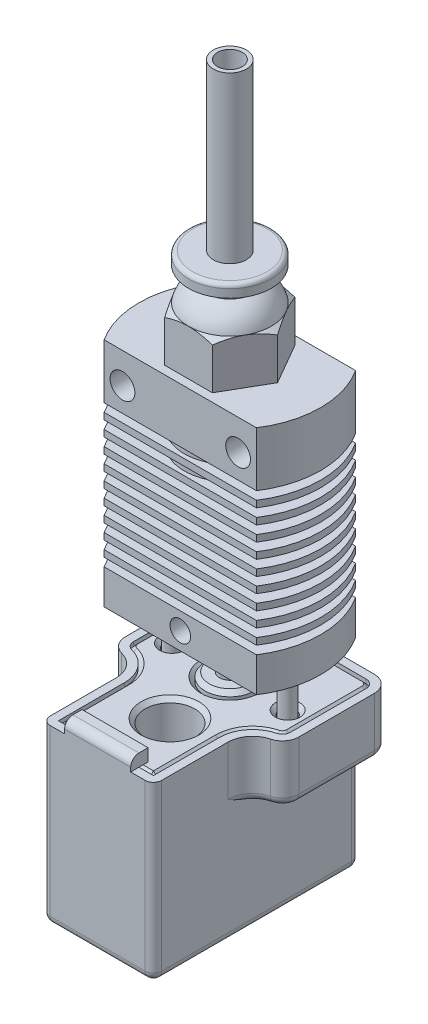
SolidWorks part; units mm, degrees
ref_plane "Front Plane" through (0, 0, 0) normal (0, 0, 1) x (1, 0, 0)
ref_plane "Top Plane" through (0, 0, 0) normal (0, 1, 0) x (1, 0, 0)
ref_plane "Right Plane" through (0, 0, 0) normal (1, 0, 0) x (0, 0, -1)
sketch "Sketch3" plane through (0, 0, 0) normal (0, 1, 0) x (1, 0, 0)
  line L1 (-9.2195, 6) -> (9.2195, 6)
  line L3 (-9.2195, -6) -> (9.2195, -6)
  arc A0 (-9.2195, 6) -> (-9.2195, -6) centre (0, 0) ccw
  arc A1 (9.2195, -6) -> (9.2195, 6) centre (0, 0) ccw
extrude "Boss-Extrude1" add sketch "Sketch3" along normal blind 28
sketch "Sketch5" plane through (0, 0, 0) normal (0, 0, 1) x (1, 0, 0)
  line L0 (0, 28) -> (0, 25.8) construction
  line L1 (-9.2195, 28) -> (9.2195, 28) construction
  line L2 (0, 25.8) -> (0, 22.8) construction
  line L3 (-7, 24.3) -> (7, 24.3) construction
  circle A0 centre (7, 24.3) radius 1.5
  circle A1 centre (-7, 24.3) radius 1.5
  point P9 (0, 24.3)
extrude "Cut-Extrude1" cut sketch "Sketch5" against normal through all and the other way through all
sketch "Sketch6" plane through (0, 0, 0) normal (0, 0, 1) x (1, 0, 0)
  line L0 (0, 28) -> (4.5, 28)
  line L1 (-9.2195, 28) -> (9.2195, 28) construction
  line L2 (0, 28) -> (0, 19.5) construction
  line L3 (4.5, 28) -> (4.5, 19.5)
  line L4 (0, 19.5) -> (3.5, 19.5) construction
  line L5 (4.5, 19.5) -> (3.5, 18.5)
  line L6 (3.5, 18.5) -> (3.5, 0)
  line L7 (3.5, 0) -> (0, 0)
  line L8 (0, 0) -> (0, 28)
  line L9 (11.9658, 28) -> (11.9658, 21.4) construction
  line L10 (0, 21.4) -> (5.5, 21.4) construction
  line L11 (5.5, 19.6) -> (5.5, 18.6)
  line L12 (5.5, 21.4) -> (11.97, 21.4)
  line L13 (5.5, 21.4) -> (5.5, 20.4)
  line L14 (5.5, 20.4) -> (11.97, 20.4)
  line L15 (11.97, 21.4) -> (11.97, 20.4)
  line L16 (5.5, 19.6) -> (11.97, 19.6)
  line L17 (11.97, 19.6) -> (11.97, 18.6)
  line L18 (5.5, 18.6) -> (11.97, 18.6)
  line L19 (0, 16.0604) -> (4, 16.0604) construction
  line L20 (11.97, 18.6) -> (11.97, 17.8) construction
  line L21 (11.97, 15) -> (4, 15)
  line L22 (11.97, 17.8) -> (4, 17.8)
  line L23 (11.97, 17.8) -> (11.97, 16.8)
  line L24 (11.97, 16.8) -> (4, 16.8)
  line L25 (4, 17.8) -> (4, 16.8)
  line L26 (4, 16) -> (4, 15)
  line L27 (11.97, 16) -> (4, 16)
  line L28 (11.97, 16) -> (11.97, 15)
  line L29 (11.97, 13.2) -> (4, 13.2)
  line L30 (4, 14.2) -> (4, 13.2)
  line L31 (11.97, 14.2) -> (4, 14.2)
  line L32 (11.97, 14.2) -> (11.97, 13.2)
  line L33 (11.97, 11.4) -> (4, 11.4)
  line L34 (4, 12.4) -> (4, 11.4)
  line L35 (11.97, 12.4) -> (4, 12.4)
  line L36 (11.97, 12.4) -> (11.97, 11.4)
  line L37 (11.97, 9.6) -> (4, 9.6)
  line L38 (4, 10.6) -> (4, 9.6)
  line L39 (11.97, 10.6) -> (4, 10.6)
  line L40 (11.97, 10.6) -> (11.97, 9.6)
  line L41 (11.97, 7.8) -> (4, 7.8)
  line L42 (4, 8.8) -> (4, 7.8)
  line L43 (11.97, 8.8) -> (4, 8.8)
  line L44 (11.97, 8.8) -> (11.97, 7.8)
  line L45 (11.97, 6) -> (4, 6)
  line L46 (4, 7) -> (4, 6)
  line L47 (11.97, 7) -> (4, 7)
  line L48 (11.97, 7) -> (11.97, 6)
  line L49 (11.97, 4.2) -> (4, 4.2)
  line L50 (4, 5.2) -> (4, 4.2)
  line L51 (11.97, 5.2) -> (4, 5.2)
  line L52 (11.97, 5.2) -> (11.97, 4.2)
  dimension "D1" = 2
  dimension "D2" = 8
revolve "Cut-Revolve1" cut sketch "Sketch6" angle 360 about L8
sketch "Sketch7" plane through (0, 0, 6) normal (0, 0, 1) x (1, 0, 0)
  line L0 (0, 0) -> (0, 4.2) construction
  line L1 (9.2195, 4.2) -> (-9.2195, 4.2) construction
  circle A0 centre (0, 2.1) radius 1.25
extrude "Cut-Extrude2" cut sketch "Sketch7" against normal blind 5
ref_plane "Plane1" through (0, -5.7, 0) normal (0, 1, 0) x (1, 0, 0)
sketch "Sketch9" plane through (0, -5.7, 0) normal (0, 1, 0) x (1, 0, 0)
  line L0 (0, 0) -> (0, -15) construction
  line L1 (0, 0) -> (0, 8) construction
  line L2 (-5.75, 0) -> (5.75, 0) construction
  line L3 (8.1234, 0) -> (8.1234, -8) construction
  line L4 (-5.75, 8) -> (5.75, 8)
  line L5 (-5.75, 8) -> (-5.75, -15)
  line L6 (-5.75, -15) -> (5.75, -15)
  line L7 (5.75, 8) -> (5.75, -15)
  line L8 (5.75, -8) -> (0.75, -8) construction
  circle A0 centre (0, 0) radius 3
  circle A1 centre (0.75, -8) radius 3
  point P6 (0, 0)
extrude "Boss-Extrude2" add sketch "Sketch9" against normal blind 20 separate body
sketch "Sketch10" plane through (0, -5.7, 0) normal (0, 1, 0) x (1, 0, 0)
  line L0 (0, 8) -> (0, -3) construction
  line L1 (5.75, 8) -> (-5.75, 8) construction
  line L2 (5.75, -15) -> (5.75, 8) construction
  line L3 (-9.5, 8) -> (-5.75, 8)
  line L4 (-9.5, 8) -> (-9.5, -3)
  line L5 (-9.5, -3) -> (-5.75, -3)
  line L6 (9.5, 8) -> (9.5, -3)
  line L7 (-9.5, 8) -> (9.5, -3) construction
  line L8 (-9.5, -3) -> (9.5, 8) construction
  line L9 (-5.75, 8) -> (-5.75, -15) construction
  line L10 (5.75, -3) -> (5.75, 8)
  line L11 (-5.75, 8) -> (-5.75, -3)
  line L12 (5.75, -3) -> (9.5, -3)
  line L13 (5.75, 8) -> (9.5, 8)
  point P5 (0, 2.5)
  line M4 (-5.75, 8) -> (-5.75, -15)
  line M6 (5.75, -15) -> (5.75, 8)
extrude "Boss-Extrude3" add sketch "Sketch10" against normal blind 6 contours L4 L5 L3 M4 | L13 L12 L6 M6 region at (-7.625, -5.7, -2.5) region at (7.625, -5.7, -2.5)
sketch "Sketch8" plane through (0, -5.7, 0) normal (0, 1, 0) x (1, 0, 0)
  line L0 (-7, 0) -> (7, 0) construction
  circle A0 centre (7, 0) radius 1
  circle A1 centre (-7, 0) radius 1
  point P5 (0, 0)
extrude "Cut-Extrude3" cut sketch "Sketch8" along normal up to vertex (9.9 mm away) and the other way through all up to point (-9.2195, 4.2, 6)
sketch "Sketch11" plane through (0, -11.7, 0) normal (0, -1, 0) x (1, 0, 0)
  circle A0 centre (7, 0) radius 2
  circle A1 centre (-7, 0) radius 1
  circle A2 centre (-7, 0) radius 1 construction
  circle A3 centre (7, 0) radius 1
  circle A4 centre (7, 0) radius 1 construction
  circle A5 centre (-7, 0) radius 2
  dimension "D1" = 0
  dimension "D2" = 0
extrude "Cut-Extrude4" cut sketch "Sketch11" against normal blind 2 and the other way through all
sketch "Sketch12" plane through (-5.75, 0, 0) normal (-1, 0, 0) x (0, 0, 1)
  line L0 (15, -5.7) -> (15, -15.7) construction
  line L2 (15, -25.7) -> (15, -5.7) construction
  line L3 (15, -15.7) -> (10, -15.7) construction
  circle A0 centre (10, -15.7) radius 1
extrude "Cut-Extrude5" cut sketch "Sketch12" against normal blind 6.5
fillet "Fillet1" radius 4 2 edges at (-5.75, -8.7, 3) (5.75, -8.7, 3)
fillet "Fillet2" radius 1 7 edges at (-9.5, -8.7, -8) (9.5, -8.7, -8) (0, -25.7, 15) (9.5, -8.7, 3) (-9.5, -8.7, 3) (5.75, -18.7, -8) (-5.75, -18.7, -8)
chamfer "Chamfer1" distance 0.5 angle 45 42 edges at (-7, -5.7, 1) (7, -5.7, 1) (0, -5.7, 3) (0, -25.7, 3) (0.75, -25.7, 11) (6.625, -11.7, -8) (9.2071, -11.7, -7.7071) (9.5, -11.7, -2.4245) (9.2906, -11.7, 2.7633) (6.5877, -11.7, 4.5427) (-6.625, -11.7, -8) (-9.2071, -11.7, -7.7071) (-9.5, -11.7, -2.4245) (-9.2906, -11.7, 2.7633) (-6.5877, -11.7, 4.5427) (-5, -25.7, 0) (-5.75, -25.7, -4.2806) (-5.4571, -25.7, -7.7071) (0, -25.7, -8) (5.4571, -25.7, -7.7071) (5.75, -25.7, -4.2806) (5, -25.7, 0) (-5.75, -5.7, 10.9961) (-6.5877, -5.7, 4.5427) (-9.2906, -5.7, 2.7633) (-9.5, -5.7, -2.4245) (-9.2071, -5.7, -7.7071) (0, -5.7, -8) (9.2071, -5.7, -7.7071) (9.5, -5.7, -2.4245) (-5.75, -25.7, 7.7806) (5.75, -25.7, 7.7806) (9.2906, -5.7, 2.7633) (-5.75, -25.4071, 14.7071) (5.75, -25.4071, 14.7071) (6.5877, -5.7, 4.5427) (-5.75, -15.2, 15) (0, -5.7, 15) (5.75, -15.2, 15) (5.75, -5.7, 10.9961) (0.75, -5.7, 11) (-5.75, -15.7, 11)
sketch "Sketch13" plane through (0, 0, 0) normal (0, 0, 1) x (1, 0, 0)
  line L0 (3.5, -5.7) -> (-3.5, -5.7) construction
  line L1 (3, -6.2) -> (-3, -6.2) construction
  line L2 (-3.5, -25.7) -> (3.5, -25.7) construction
  line L3 (3.5, 18.5) -> (-3.5, 18.5) construction
  line L4 (-3.5, 0) -> (3.5, 0) construction
  line L5 (3.5, -5.7) -> (-3.5, -5.7) construction
  line L6 (3, -6.2) -> (-3, -6.2) construction
  line L7 (-3.5, -25.7) -> (3.5, -25.7) construction
  line L8 (3.5, 18.5) -> (-3.5, 18.5) construction
  line L9 (-3.5, 0) -> (3.5, 0) construction
  line L10 (0, -25.7) -> (0, -26.2) construction
  line L11 (0, -25.7) -> (0, -31.2) construction
  line L12 (0, -31.2) -> (0, -10.2) construction
  line L13 (-3, -10.2) -> (-3, -5.2)
  line L14 (0, -5.2) -> (-1.25, -5.2) construction
  line L15 (-3, -5.2) -> (-1.25, -5.2)
  line L16 (-1.25, -5.2) -> (-1.25, -2.7)
  line L17 (-1.25, -2.7) -> (-3.5, -2.7)
  line L18 (-3.5, -2.7) -> (-3.5, 18.5)
  line L19 (-3.5, 18.5) -> (-2.5, 18.5)
  line L20 (-2.5, 18.5) -> (-2.5, 15.5)
  line L21 (0, 15.5) -> (-1, 15.5) construction
  line L22 (-2.5, 15.5) -> (-1, 14)
  line L23 (-1, 14) -> (-1, -10.2)
  line L24 (-1, -10.2) -> (-3, -10.2)
  line L25 (0, 0) -> (0, -2.0747) construction
  point P16 (0, -26.2)
revolve "Revolve1" add sketch "Sketch13" angle 360 about L25
chamfer "Chamfer2" distance 0.5 angle 45 2 edges at (0, -2.7, 3.5) (0, -5.2, 3)
sketch "Sketch14" plane through (0, -9.7, 0) normal (0, -1, 0) x (1, 0, 0)
  circle A1 centre (-7, 0) radius 1
  circle A2 centre (-7, 0) radius 1 construction
  circle A3 centre (7, 0) radius 1
  circle A4 centre (7, 0) radius 1 construction
  circle A5 centre (7, 0) radius 1.75
  circle A6 centre (-7, 0) radius 1.75
  dimension "D1" = 0
  dimension "D2" = 0
extrude "Boss-Extrude4" add sketch "Sketch14" along normal blind 2 separate body
sketch "Sketch15" plane through (0, -9.7, 0) normal (0, -1, 0) x (1, 0, 0)
  circle A0 centre (-7, 0) radius 1 construction
  circle A1 centre (7, 0) radius 1 construction
  circle A2 centre (-7, 0) radius 1 construction
  circle A3 centre (7, 0) radius 1 construction
  circle A4 centre (7, 0) radius 0.9
  circle A5 centre (-7, 0) radius 0.9
extrude "Boss-Extrude5" add sketch "Sketch15" against normal blind 14
sketch "Sketch16" plane through (0, 28, 0) normal (0, 1, 0) x (1, 0, 0)
  line L1 (5.7735, 0) -> (2.8868, 5)
  line L2 (2.8868, 5) -> (-2.8868, 5)
  line L3 (-2.8868, 5) -> (-5.7735, 0)
  line L4 (-5.7735, 0) -> (-2.8868, -5)
  line L5 (-2.8868, -5) -> (2.8868, -5)
  line L6 (2.8868, -5) -> (5.7735, 0)
  circle A0 centre (0, 0) radius 5 construction
  circle A1 centre (0, 0) radius 1.5
extrude "Boss-Extrude6" add sketch "Sketch16" along normal blind 8 separate body
sketch "Sketch17" plane through (0, 0, 0) normal (0, 0, 1) x (1, 0, 0)
  line L0 (0, 36) -> (0, 34) construction
  line L1 (-2.8868, 36) -> (2.8868, 36) construction
  line L2 (5.7735, 33.009) -> (4.9988, 33.5225)
  line L3 (5.7735, 36) -> (5.7735, 28) construction
  line L4 (0, 36) -> (3, 36) construction
  line L5 (3, 36) -> (1.332, 36.799) construction
  line L6 (3, 36) -> (7.6297, 36)
  line L7 (7.6297, 36) -> (7.6297, 33.009)
  line L8 (7.6297, 33.009) -> (5.7735, 33.009)
  arc A0 (3, 36) -> (4.9988, 33.5225) centre (1.4036, 32.667) cw
revolve "Cut-Revolve2" cut sketch "Sketch17" angle 360 about L0
sketch "Sketch18" plane through (0, 0, 0) normal (0, 0, 1) x (1, 0, 0)
  line L0 (0, 36) -> (0, 39) construction
  line L1 (1.5, 36) -> (-1.5, 36) construction
  line L2 (0, 39) -> (1.25, 39) construction
  line L3 (1.25, 38.5) -> (1.25, 31)
  line L4 (0, 39) -> (5, 39) construction
  line L5 (1.75, 37.5) -> (1.75, 31)
  line L6 (1.75, 39) -> (4.5, 39)
  line L8 (1.75, 37.5) -> (5, 37.5)
  line L9 (5, 38.5) -> (5, 37.5)
  line L10 (1.75, 39) -> (1.75, 31) construction
  line L11 (1.25, 31) -> (1.75, 31)
  line L12 (1.25, 39) -> (1.25, 31) construction
  arc A0 (5, 38.5) -> (4.5, 39) centre (4.5, 38.5) ccw
  arc A1 (1.75, 39) -> (1.25, 38.5) centre (1.75, 38.5) ccw
  dimension "D2" = 0.5
  dimension "D1" = 0.5
revolve "Revolve2" add sketch "Sketch18" angle 360 about L0
sketch "Sketch19" plane through (0, 39, 0) normal (0, 1, 0) x (1, 0, 0)
  circle A0 centre (0, 0) radius 2
extrude "Extrude-Thin1" add sketch "Sketch19" along normal blind 20 and the other way blind 10 separate body thin thin type one direction reverse wall 0.5
sketch "Sketch20" plane through (0, -25.7, 0) normal (0, -1, 0) x (1, 0, 0)
  line L0 (8.5, -8) -> (4.75, -8) construction
  line L1 (-5.75, 15) -> (5.75, 15) construction
  line L2 (-5.75, 15) -> (-5.75, -8) construction
  line L3 (-5.75, -8) -> (5.75, -8) construction
  line L4 (5.75, 15) -> (5.75, -8) construction
  line L5 (-5.75, 16) -> (5.75, 16)
  line L6 (6.75, 15) -> (6.75, -8)
  line L7 (-5.75, -9) -> (5.75, -9)
  line L8 (-6.75, 15) -> (-6.75, -8)
  line L9 (-6.75, -9) -> (6.75, -9) construction
  line L10 (-6.75, 16) -> (-6.75, -9) construction
  line L11 (6.75, 16) -> (6.75, -9) construction
  line L12 (-6.75, 16) -> (6.75, 16) construction
  arc A0 (-5.75, -9) -> (-6.75, -8) centre (-5.75, -8) cw
  arc A1 (6.75, -8) -> (5.75, -9) centre (5.75, -8) cw
  arc A2 (5.75, 16) -> (6.75, 15) centre (5.75, 15) cw
  arc A3 (-5.75, 16) -> (-6.75, 15) centre (-5.75, 15) ccw
  dimension "D2" = 1
  dimension "D1" = 1
extrude "Extrude-Thin2" add sketch "Sketch20" against normal blind 14 separate body thin thin type one direction reverse wall 1
sketch "Sketch21" plane through (0, -11.7, 0) normal (0, 1, 0) x (1, 0, 0)
  line L0 (-9.5, 7) -> (-9.5, -2.151) construction
  line L2 (-9.5, 7) -> (-9.5, -2.151) construction
  line L3 (-5.75, -6.9922) -> (-5.75, -15) construction
  line L4 (0, 0) -> (0, 6) construction
  line L5 (9.2195, 6) -> (-9.2195, 6) construction
  line L6 (-8.5, 8) -> (8.5, 8) construction
  line L7 (9.5, 7) -> (9.5, -2.151) construction
  line L8 (-5.75, -15) -> (5.75, -15) construction
  line L9 (5.75, -15) -> (5.75, -6.9922) construction
  line L10 (-10.5, 7) -> (-10.5, -2.151)
  line L11 (-6.75, -6.9922) -> (-6.75, -15)
  line L12 (-5.75, -16) -> (5.75, -16)
  line L13 (6.75, -15) -> (6.75, -6.9922)
  line L14 (10.5, 7) -> (10.5, -2.151)
  line L15 (-8.5, 9) -> (8.5, 9)
  line L16 (-6.75, -16) -> (6.75, -16) construction
  line L17 (6.75, -16) -> (6.75, -6.9922) construction
  line L18 (-6.75, -6.9922) -> (-6.75, -16) construction
  arc A0 (-5.75, -6.9922) -> (-8.75, -3.1192) centre (-9.75, -6.9922) ccw construction
  arc A1 (-9.5, -2.151) -> (-8.75, -3.1192) centre (-8.5, -2.151) ccw construction
  arc A2 (-8.5, 8) -> (-9.5, 7) centre (-8.5, 7) ccw construction
  arc A3 (-5.75, -6.9922) -> (-8.75, -3.1192) centre (-9.75, -6.9922) ccw construction
  arc A4 (-9.5, -2.151) -> (-8.75, -3.1192) centre (-8.5, -2.151) ccw construction
  arc A5 (-8.5, 8) -> (-9.5, 7) centre (-8.5, 7) ccw construction
  arc A6 (8.5, 8) -> (9.5, 7) centre (8.5, 7) cw construction
  arc A7 (9.5, -2.151) -> (8.75, -3.1192) centre (8.5, -2.151) cw construction
  arc A8 (5.75, -6.9922) -> (8.75, -3.1192) centre (9.75, -6.9922) cw construction
  arc A9 (-10.5, -2.151) -> (-9, -4.0874) centre (-8.5, -2.151) ccw
  arc A10 (-6.75, -6.9922) -> (-9, -4.0874) centre (-9.75, -6.9922) ccw
  arc A11 (6.75, -6.9922) -> (9, -4.0874) centre (9.75, -6.9922) cw
  arc A12 (10.5, -2.151) -> (9, -4.0874) centre (8.5, -2.151) cw
  arc A13 (8.5, 9) -> (10.5, 7) centre (8.5, 7) cw
  arc A14 (-8.5, 9) -> (-10.5, 7) centre (-8.5, 7) ccw
  arc A15 (5.75, -16) -> (6.75, -15) centre (5.75, -15) ccw
  arc A16 (-6.75, -15) -> (-5.75, -16) centre (-5.75, -15) ccw
  dimension "D2" = 1
  dimension "D1" = 1
extrude "Extrude-Thin3" add sketch "Sketch21" along normal blind 6 thin thin type one direction reverse wall 1
sketch "Sketch22" plane through (0, -11.7, 0) normal (0, -1, 0) x (1, 0, 0)
  line L0 (6.75, 6.9922) -> (6.75, 4.3464) construction
  line L3 (5.75, -9) -> (8.5, -9) construction
  line L4 (10.5, -7) -> (10.5, 2.151) construction
  line L7 (-6.75, 4.3464) -> (-6.75, 6.9922) construction
  line L8 (-10.5, 2.151) -> (-10.5, -7) construction
  line L9 (-8.5, -9) -> (-5.75, -9) construction
  line L10 (6.75, 6.9922) -> (6.75, -8)
  line L13 (5.75, -9) -> (8.5, -9)
  line L14 (10.5, -7) -> (10.5, 2.151)
  line L17 (-6.75, -8) -> (-6.75, 6.9922)
  line L18 (-10.5, 2.151) -> (-10.5, -7)
  line L19 (-8.5, -9) -> (-5.75, -9)
  arc A3 (5.75, -9) -> (6.75, -8) centre (5.75, -8) ccw construction
  arc A4 (8.5, -9) -> (10.5, -7) centre (8.5, -7) ccw construction
  arc A5 (10.5, 2.151) -> (9, 4.0874) centre (8.5, 2.151) ccw construction
  arc A6 (6.75, 6.9922) -> (9, 4.0874) centre (9.75, 6.9922) ccw construction
  arc A7 (-6.75, -8) -> (-5.75, -9) centre (-5.75, -8) ccw construction
  arc A11 (-9, 4.0874) -> (-6.75, 6.9922) centre (-9.75, 6.9922) ccw construction
  arc A12 (-9, 4.0874) -> (-10.5, 2.151) centre (-8.5, 2.151) ccw construction
  arc A13 (-10.5, -7) -> (-8.5, -9) centre (-8.5, -7) ccw construction
  arc A17 (5.75, -9) -> (6.75, -8) centre (5.75, -8) ccw
  arc A18 (8.5, -9) -> (10.5, -7) centre (8.5, -7) ccw
  arc A19 (10.5, 2.151) -> (9, 4.0874) centre (8.5, 2.151) ccw
  arc A20 (6.75, 6.9922) -> (9, 4.0874) centre (9.75, 6.9922) ccw
  arc A21 (-6.75, -8) -> (-5.75, -9) centre (-5.75, -8) ccw
  arc A25 (-9, 4.0874) -> (-6.75, 6.9922) centre (-9.75, 6.9922) ccw
  arc A26 (-9, 4.0874) -> (-10.5, 2.151) centre (-8.5, 2.151) ccw
  arc A27 (-10.5, -7) -> (-8.5, -9) centre (-8.5, -7) ccw
extrude "Boss-Extrude8" add sketch "Sketch22" along normal blind 1
sketch "Sketch23" plane through (0, -25.7, 0) normal (0, -1, 0) x (1, 0, 0)
  line L4 (-5.75, -9) -> (5.75, -9)
  line L5 (6.75, -8) -> (6.75, 15)
  line L6 (5.75, 16) -> (-5.75, 16)
  line L7 (-6.75, 15) -> (-6.75, -8)
  line L8 (-5.75, -9) -> (5.75, -9)
  line L9 (6.75, -8) -> (6.75, 15)
  line L10 (5.75, 16) -> (-5.75, 16)
  line L11 (-6.75, 15) -> (-6.75, -8)
  circle A0 centre (0, 0) radius 5
  arc A4 (-6.75, -8) -> (-5.75, -9) centre (-5.75, -8) ccw
  arc A5 (5.75, -9) -> (6.75, -8) centre (5.75, -8) ccw
  arc A6 (6.75, 15) -> (5.75, 16) centre (5.75, 15) ccw
  arc A7 (-5.75, 16) -> (-6.75, 15) centre (-5.75, 15) ccw
  arc A8 (-6.75, -8) -> (-5.75, -9) centre (-5.75, -8) ccw
  arc A9 (5.75, -9) -> (6.75, -8) centre (5.75, -8) ccw
  arc A10 (6.75, 15) -> (5.75, 16) centre (5.75, 15) ccw
  arc A11 (-5.75, 16) -> (-6.75, 15) centre (-5.75, 15) ccw
  dimension "D1" = 0
extrude "Boss-Extrude9" add sketch "Sketch23" along normal blind 1
sketch "Sketch24" plane through (0, -5.7, 0) normal (0, 1, 0) x (1, 0, 0)
  line L0 (0, 9) -> (-4, 9)
  line L1 (8.5, 9) -> (-8.5, 9) construction
  line L2 (-4, 9) -> (-4, 6.9)
  line L4 (-4, 6.9) -> (4, 6.9)
  line L5 (4, 6.9) -> (4, 9)
  line L6 (4, 9) -> (0, 9)
  line L7 (-4, -16) -> (-4, -13.9)
  line L8 (-5.75, -16) -> (5.75, -16) construction
  line L9 (-4, -13.9) -> (4, -13.9)
  line L10 (4, -13.9) -> (4, -16)
  line L11 (4, -16) -> (-4, -16)
extrude "Boss-Extrude10" add sketch "Sketch24" along normal blind 1.5
fillet "Fillet3" radius 1 20 edges at (-7.3783, -12.7, 5.1551) (-10.0811, -12.7, 3.3757) (-7.125, -12.7, -9) (-9.9142, -12.7, -8.4142) (7.125, -12.7, -9) (9.9142, -12.7, -8.4142) (7.3783, -12.7, 5.1551) (10.0811, -12.7, 3.3757) (6.4571, -26.7, -8.7071) (0, -26.7, -9) (-6.4571, -26.7, -8.7071) (-6.75, -26.7, 3.5) (-6.4571, -26.7, 15.7071) (0, -26.7, 16) (6.4571, -26.7, 15.7071) (-10.5, -12.7, -2.4245) (10.5, -12.7, -2.4245) (6.75, -26.7, 3.5) (0, -4.2, -9) (0, -4.2, 16)
